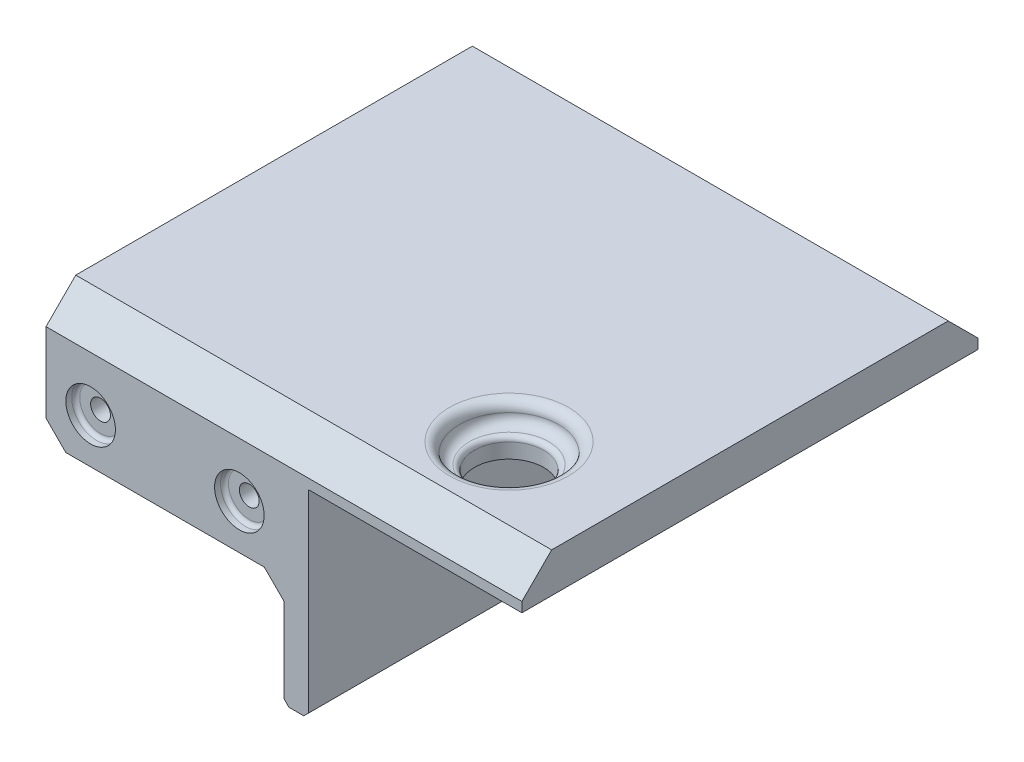
SolidWorks part; units mm, degrees
ref_plane "Спереди" through (0, 0, 0) normal (0, 0, 1) x (1, 0, 0)
ref_plane "Сверху" through (0, 0, 0) normal (0, 1, 0) x (1, 0, 0)
ref_plane "Справа" through (0, 0, 0) normal (1, 0, 0) x (0, 0, -1)
sketch "Эскиз1" plane through (0, 0, 0) normal (0, 0, 1) x (1, 0, 0)
  line L0 (0, 0) -> (0, -64.8775) construction
  line L1 (-4.9497, 4.9497) -> (4.9497, 4.9497) construction
  line L2 (-4.9497, 4.9497) -> (-4.9497, -4.9497) construction
  line L3 (-4.9497, -4.9497) -> (4.9497, -4.9497) construction
  line L4 (4.9497, 4.9497) -> (4.9497, -4.9497) construction
  line L5 (-4.9497, 4.9497) -> (4.9497, -4.9497) construction
  line L6 (-4.9497, -4.9497) -> (4.9497, 4.9497) construction
  line L7 (0, -64.8775) -> (14.6, -64.8775) construction
  line L8 (24.6, -34.8775) -> (4.6, -34.8775) construction
  line L9 (24.6, -34.8775) -> (24.6, -74.8775) construction
  line L10 (4.6, -34.8775) -> (4.6, -74.8775) construction
  line L11 (4.6, -74.8775) -> (24.6, -74.8775) construction
  line L12 (14.6, -73.302) -> (14.6, -29.9429) construction
  line L13 (2.6, -28.8775) -> (26.6, -28.8775)
  line L14 (2.6, -28.8775) -> (2.6, -48.8775)
  line L15 (2.6, -48.8775) -> (26.6, -48.8775)
  line L16 (26.6, -28.8775) -> (26.6, -48.8775)
  circle A0 centre (0, 0) radius 3.25 construction
  circle A1 centre (-4.9497, 4.9497) radius 1.4 construction
  circle A2 centre (4.9497, 4.9497) radius 1.4 construction
  circle A3 centre (4.9497, -4.9497) radius 1.4 construction
  circle A4 centre (-4.9497, -4.9497) radius 1.4 construction
  circle A5 centre (0, 0) radius 10 construction
  circle A6 centre (7.1, -37.3775) radius 1
  circle A7 centre (22.1, -37.3775) radius 1
  circle A8 centre (7.1, -52.3775) radius 1 construction
  circle A9 centre (22.1, -52.3775) radius 1 construction
  circle A11 centre (14.6, -64.8775) radius 10 construction
  circle A12 centre (14.6, -37.8775) radius 1
  circle A13 centre (21.6, -44.8775) radius 1
  circle A14 centre (7.6, -44.8775) radius 1
  point P3 (0, 0)
  point P50 (32.6, -34.8775)
  dimension "D1" = 6.5
  dimension "D3" = 2.8
  dimension "D6" = 20
  dimension "D9" = 2
  dimension "D15" = 6
  dimension "D16" = 10
  dimension "D17" = 14
  dimension "D2" = 14
  dimension "D4" = 66.5
  dimension "D5" = 14.6
  dimension "D7" = 27.5
  dimension "D8" = 7.5
  dimension "D10" = 15
  dimension "D11" = 15
  dimension "D12" = 30
  dimension "D13" = 20
  dimension "D14" = 40
  dimension "D18" = 24
  dimension "D19" = 7
  dimension "D24" = 27
  dimension "D25" = 7
  dimension "D26" = 7
extrude "Бобышка-Вытянуть1" add sketch "Эскиз1" along normal blind 3
sketch "Эскиз2" plane through (0, 0, 3) normal (0, 0, 1) x (1, 0, 0)
  line L0 (26.6, -48.8775) -> (26.6, -28.8775) construction
  line L1 (2.6, -28.8775) -> (26.6, -28.8775)
  line L2 (2.6, -28.8775) -> (2.6, -32.8775)
  line L3 (2.6, -32.8775) -> (26.6, -32.8775)
  line L4 (26.6, -28.8775) -> (26.6, -32.8775)
  dimension "D1" = 4
extrude "Бобышка-Вытянуть2" add sketch "Эскиз2" along normal blind 40
sketch "Эскиз3" plane through (0, 0, 43) normal (0, 0, 1) x (1, 0, 0)
  line L1 (26.6, -28.8775) -> (2.6, -28.8775) construction
  line L4 (26.6, -48.8775) -> (26.6, -32.8775) construction
  line L5 (26.6, -28.8775) -> (2.6, -28.8775)
  line L6 (2.6, -28.8775) -> (26.6, -28.8775)
  line L7 (2.6, -28.8775) -> (2.6, -41.8775)
  line L8 (2.6, -41.8775) -> (26.6, -41.8775)
  line L9 (26.6, -28.8775) -> (26.6, -41.8775)
  circle A0 centre (22.1, -37.3775) radius 1 construction
  circle A1 centre (7.1, -37.3775) radius 1 construction
  circle A2 centre (22.1, -37.3775) radius 1
  circle A3 centre (7.1, -37.3775) radius 1
  line M1 (2.6, -28.8775) -> (2.6, -32.8775)
  line M2 (2.6, -32.8775) -> (26.6, -32.8775)
  line M3 (26.6, -32.8775) -> (26.6, -28.8775)
  line M4 (26.6, -28.8775) -> (2.6, -28.8775)
  dimension "D1" = 13
extrude "Бобышка-Вытянуть3" add sketch "Эскиз3" along normal blind 3 contours M4 M1 M2 M3 | L9 L7 L8 A3 A2 M2
sketch "Эскиз4" plane through (0, 0, 3) normal (0, 0, 1) x (1, 0, 0)
  circle A0 centre (7.1, -37.3775) radius 1 construction
  circle A1 centre (22.1, -37.3775) radius 1 construction
  circle A2 centre (7.1, -37.3775) radius 1
  circle A3 centre (22.1, -37.3775) radius 1
extrude "Бобышка-Вытянуть4" add sketch "Эскиз4" against normal up to surface (3 mm away) up to face at (22.6, -44.8775, 0)
chamfer "Фаска1" distance 2 angle 45 2 edges
sketch "Эскиз5" plane through (0, 0, 46) normal (0, 0, 1) x (1, 0, 0)
  circle A0 centre (7.1, -37.3775) radius 2.5
  circle A1 centre (22.1, -37.3775) radius 2.5
  dimension "D1" = 5
extrude "Вырез-Вытянуть1" cut sketch "Эскиз5" against normal blind 1
sketch "Эскиз6" plane through (0, 0, 0) normal (0, 0, -1) x (-1, 0, 0)
  circle A0 centre (-14.6, -37.8775) radius 2.5
  circle A1 centre (-7.6, -44.8775) radius 2.5
  circle A2 centre (-21.6, -44.8775) radius 2.5
  dimension "D1" = 5
extrude "Вырез-Вытянуть2" cut sketch "Эскиз6" against normal blind 1
fillet "Скругление1" radius 0.4 5 edges at (24.6, -37.3775, 45) (9.6, -37.3775, 45) (5.1, -44.8775, 1) (19.1, -44.8775, 1) (12.1, -37.8775, 1)
chamfer "Фаска3" distance 2 angle 45 4 edges at (2.6, -41.8775, 44.5) (26.6, -41.8775, 44.5) (26.6, -48.8775, 1.5) (2.6, -48.8775, 1.5)
sketch "Эскиз7" [suppressed] plane through (0, -32.8775, 0) normal (0, -1, 0) x (1, 0, 0)
  line L0 (14.6, 41) -> (14.6, 5) construction
  line L1 (26.6, 41) -> (2.6, 41) construction
  line L2 (2.6, 5) -> (26.6, 5) construction
  line L3 (2.6, 23) -> (26.6, 23) construction
  line L4 (2.6, 41) -> (2.6, 5) construction
  line L5 (26.6, 41) -> (26.6, 5) construction
  line L7 (13.6, 19) -> (15.6, 19)
  line L8 (12.6, 20) -> (12.6, 26)
  line L9 (13.6, 27) -> (15.6, 27)
  line L10 (16.6, 20) -> (16.6, 26)
  line L11 (12.6, 19) -> (16.6, 27) construction
  line L12 (12.6, 27) -> (16.6, 19) construction
  circle A0 centre (7.1, 38) radius 1.75
  circle A1 centre (22.1, 38) radius 1.75
  circle A2 centre (22.1, 8) radius 1.75
  circle A3 centre (7.1, 8) radius 1.75
  circle A4 centre (14.6, 32) radius 1.75
  circle A5 centre (14.6, 14) radius 1.75
  circle A6 centre (7.1, 23) radius 1.75
  circle A7 centre (22.1, 23) radius 1.75
  arc A8 (13.6, 19) -> (12.6, 20) centre (13.6, 20) cw
  arc A9 (15.6, 19) -> (16.6, 20) centre (15.6, 20) ccw
  arc A10 (15.6, 27) -> (16.6, 26) centre (15.6, 26) cw
  arc A11 (12.6, 26) -> (13.6, 27) centre (13.6, 26) cw
  point P28 (14.6, 23)
  dimension "D3" = 3.5
  dimension "D7" = 1
  dimension "D1" = 15
  dimension "D2" = 30
  dimension "D4" = 6
  dimension "D5" = 4
  dimension "D6" = 8
extrude "Вырез-Вытянуть3" [suppressed] cut sketch "Эскиз7" against normal up to surface (4 mm away)
sketch "Эскиз8" [suppressed] plane through (0, -32.8775, 0) normal (0, -1, 0) x (1, 0, 0)
  circle A0 centre (7.1, 38) radius 3
  circle A1 centre (22.1, 38) radius 3
  circle A2 centre (14.6, 32) radius 3
  circle A3 centre (22.1, 23) radius 3
  circle A4 centre (14.6, 14) radius 3
  circle A5 centre (7.1, 23) radius 3
  circle A6 centre (22.1, 8) radius 3
  circle A7 centre (7.1, 8) radius 3
  dimension "D1" = 6
extrude "Вырез-Вытянуть4" [suppressed] cut sketch "Эскиз8" against normal blind 0.5
fillet "Скругление2" [suppressed] radius 0.5
sketch "Эскиз9" plane through (26.6, 0, 0) normal (1, 0, 0) x (0, 0, -1)
  line L0 (-46, -39.8775) -> (-46, -28.8775) construction
  line L1 (0, -28.8775) -> (-46, -28.8775)
  line L2 (0, -28.8775) -> (0, -32.8775)
  line L3 (0, -32.8775) -> (-46, -32.8775)
  line L4 (-46, -28.8775) -> (-46, -32.8775)
extrude "Бобышка-Вытянуть5" add sketch "Эскиз9" along normal blind 24
chamfer "Фаска2" distance 3 angle 45 2 edges at (26.6, -28.8775, 0) (26.6, -28.8775, 46)
sketch "Эскиз10" plane through (0, -32.8775, 0) normal (0, -1, 0) x (1, 0, 0)
  line L0 (50.6, 46) -> (26.6, 46) construction
  line L1 (26.6, 0) -> (29.1, 0)
  line L2 (26.6, 0) -> (26.6, 46)
  line L3 (26.6, 46) -> (29.1, 46)
  line L4 (29.1, 0) -> (29.1, 46)
  dimension "D1" = 2.5
extrude "Бобышка-Вытянуть6" add sketch "Эскиз10" along normal blind 20
chamfer "Фаска4" distance 0.5 angle 45 2 edges at (29.1, -52.8775, 23) (26.6, -52.8775, 23)
chamfer "Фаска5" distance 2.8 angle 45 2 edges at (26.6, -39.8775, 44.5) (26.6, -46.8775, 1.5)
chamfer "Фаска6" distance 2 angle 45 2 edges at (26.6, -41.8574, 44.5) (26.6, -48.8574, 1.5)
chamfer "Фаска7" distance 2 angle 45 1 edges
sketch "Эскиз11" plane through (26.6, 0, 0) normal (-1, 0, 0) x (0, 0, 1)
  line L0 (42, -35.8775) -> (4, -35.8775) construction
  line L1 (21.5, -32.8775) -> (24.5, -32.8775)
  line L2 (21.5, -32.8775) -> (21.5, -52.3775)
  line L3 (21.5, -52.3775) -> (24.5, -52.3775)
  line L4 (24.5, -32.8775) -> (24.5, -52.3775)
  line L5 (0, -52.3775) -> (46, -52.3775) construction
  line L6 (23, -35.8775) -> (23, -51.4569) construction
  line L7 (41, -32.8775) -> (5, -32.8775) construction
  line L8 (32.5, -32.8775) -> (35.5, -32.8775)
  line L9 (32.5, -32.8775) -> (32.5, -52.3775)
  line L10 (32.5, -52.3775) -> (35.5, -52.3775)
  line L11 (35.5, -32.8775) -> (35.5, -52.3775)
  line L12 (13.5, -32.8775) -> (10.5, -32.8775)
  line L13 (13.5, -32.8775) -> (13.5, -52.3775)
  line L14 (13.5, -52.3775) -> (10.5, -52.3775)
  line L15 (10.5, -32.8775) -> (10.5, -52.3775)
  dimension "D1" = 3
  dimension "D2" = 8
  dimension "D3" = 8
extrude "Бобышка-Вытянуть7" add sketch "Эскиз11" along normal blind 1.7
chamfer "Фаска8" distance 1.7 angle 45 3 edges at (24.9, -52.3775, 12) (24.9, -52.3775, 23) (24.9, -52.3775, 34)
sketch "Эскиз12" plane through (0, -32.8775, 0) normal (0, -1, 0) x (1, 0, 0)
  circle A0 centre (39, 35.7) radius 3.5
  dimension "D1" = 7
extrude "Вырез-Вытянуть5" cut sketch "Эскиз12" against normal up to surface (4 mm away) up to face at (26.6, -28.8775, 23)
sketch "Эскиз13" plane through (0, -28.8775, 0) normal (0, 1, 0) x (1, 0, 0)
  circle A0 centre (39, -35.7) radius 5
  dimension "D1" = 10
extrude "Вырез-Вытянуть6" cut sketch "Эскиз13" against normal blind 2
fillet "Скругление3" radius 1 2 edges at (39, -30.8775, 40.7) (39, -28.8775, 40.7)
sketch "Эскиз14" plane through (0, -32.8775, 0) normal (0, -1, 0) x (1, 0, 0)
  circle A0 centre (39, 9.7) radius 2.6
  dimension "D1" = 5.2
extrude "Бобышка-Вытянуть8" add sketch "Эскиз14" along normal blind 1
fillet "Скругление4" radius 0.2 1 edges at (39, -32.8775, 12.3)
fillet "Скругление5" radius 0.5 1 edges at (39, -30.8775, 39.2)
